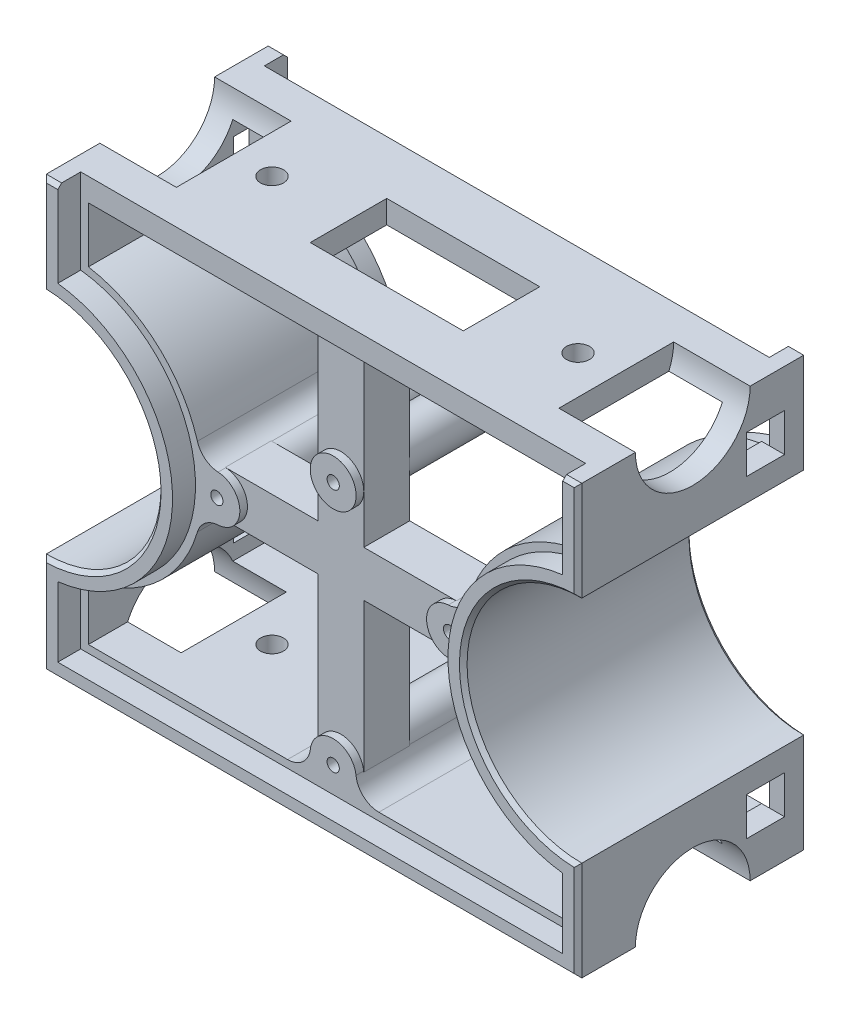
SolidWorks part; units mm, degrees
ref_plane "Front Plane" through (0, 0, 0) normal (0, 0, 1) x (1, 0, 0)
ref_plane "Top Plane" through (0, 0, 0) normal (0, 1, 0) x (1, 0, 0)
ref_plane "Right Plane" through (0, 0, 0) normal (1, 0, 0) x (0, 0, -1)
sketch "Sketch1" plane through (0, 0, 0) normal (0, 1, 0) x (1, 0, 0)
  line L1 (-35, -15) -> (35, -15)
  line L2 (-35, -15) -> (-35, 15)
  line L3 (-35, 15) -> (35, 15)
  line L4 (35, -15) -> (35, 15)
  line L5 (-35, -15) -> (35, 15) construction
  line L6 (-35, 15) -> (35, -15) construction
  point P0 (0, 0)
  dimension "D1" = 30
  dimension "D2" = 70
extrude "Boss-Extrude1" add sketch "Sketch1" along normal blind 56
sketch "Sketch2" plane through (0, 0, -15) normal (0, 0, -1) x (-1, 0, 0)
  line L0 (35, 56) -> (35, 0) construction
  line L1 (32, 53) -> (-32, 53)
  line L2 (32, 53) -> (32, 45.7482)
  line L3 (32, 3) -> (-32, 3)
  line L4 (-32, 53) -> (-32, 45.7482)
  line L5 (32, 53) -> (-32, 3) construction
  line L6 (32, 3) -> (-32, 53) construction
  line L7 (-35, 56) -> (-35, 0) construction
  line L8 (-35, 0) -> (35, 0) construction
  line L9 (-35, 56) -> (35, 56) construction
  line L10 (-32, 10.2518) -> (-32, 3)
  line L11 (32, 10.2518) -> (32, 3)
  line L12 (-33, 54) -> (-33, 44.8819)
  line L13 (33, 54) -> (33, 44.8819)
  line L14 (33, 2) -> (-33, 2)
  line L15 (-33, 11.1181) -> (-33, 2)
  line L16 (33, 11.1181) -> (33, 2)
  line L17 (33, 54) -> (-33, 54)
  arc A0 (-32, 10.2518) -> (-32, 45.7482) centre (-35, 28) ccw
  arc A1 (32, 45.7482) -> (32, 10.2518) centre (35, 28) ccw
  arc A2 (-33, 11.1181) -> (-33, 44.8819) centre (-35, 28) ccw
  arc A3 (33, 44.8819) -> (33, 11.1181) centre (35, 28) ccw
  point P0 (0, 28)
  dimension "D5" = 36
  dimension "D6" = 36
  dimension "D9" = 0
  dimension "D10" = 17
  dimension "D13" = 0
  dimension "D14" = 17
  dimension "D1" = 3
  dimension "D2" = 3
  dimension "D3" = 3
  dimension "D4" = 3
  dimension "D7" = 1
  dimension "D8" = 1
  dimension "D11" = 1
  dimension "D12" = 1
extrude "Cut-Extrude1" cut sketch "Sketch2" against normal through all contours A1 L11 L3 L10 A0 L4 L1 L2
sketch "Sketch3" plane through (0, 0, 0) normal (0, -1, 0) x (1, 0, 0)
  circle A0 centre (20, 0) radius 1.5
  circle A1 centre (-20, 0) radius 1.5
  dimension "D1" = 3
  dimension "D2" = 3
  dimension "D3" = 20
  dimension "D4" = 20
extrude "Cut-Extrude2" cut sketch "Sketch3" against normal blind 5 and the other way through all
sketch "Sketch4" plane through (35, 0, 0) normal (1, 0, 0) x (0, 0, -1)
  line L0 (-15, 56) -> (15, 56) construction
  line L1 (-15, 0) -> (15, 0) construction
  circle A0 centre (0, 56) radius 7.5
  circle A1 centre (0, 0) radius 7.5
  dimension "D1" = 15
  dimension "D2" = 15
extrude "Cut-Extrude5" cut sketch "Sketch4" against normal blind 10
sketch "Sketch6" plane through (0, 0, 15) normal (0, 0, 1) x (1, 0, 0)
  line L0 (-35, 56) -> (-35, 0) construction
  line L1 (35, 56) -> (35, 0) construction
  circle A0 centre (-35, 28) radius 15
  circle A1 centre (35, 28) radius 15
  dimension "D1" = 30
extrude "Cut-Extrude7" cut sketch "Sketch6" against normal through all
sketch "Sketch7" plane through (0, 56, 0) normal (0, 1, 0) x (1, 0, 0)
  line L1 (-10, 5) -> (10, 5)
  line L2 (-10, 5) -> (-10, -5)
  line L3 (-10, -5) -> (10, -5)
  line L4 (10, 5) -> (10, -5)
  line L5 (-10, 5) -> (10, -5) construction
  line L6 (-10, -5) -> (10, 5) construction
  point P0 (0, 0)
  dimension "D1" = 20
  dimension "D2" = 10
extrude "Cut-Extrude8" cut sketch "Sketch7" against normal blind 10
sketch "Sketch8" plane through (0, 56, 0) normal (0, 1, 0) x (1, 0, 0)
  circle A0 centre (20, 0) radius 1.5
  circle A1 centre (-20, 0) radius 1.5
  dimension "D1" = 3
  dimension "D2" = 3
  dimension "D3" = 40
  dimension "D4" = 20
extrude "Cut-Extrude10" cut sketch "Sketch8" against normal blind 10
extrude "Cut-Extrude11" cut sketch "Sketch2<3>" against normal blind 3
sketch "Sketch2<3>" plane through (0, 0, -15) normal (0, 0, -1) x (-1, 0, 0) same geometry as "Sketch2"
sketch "Sketch11" plane through (0, 0, 15) normal (0, 0, 1) x (1, 0, 0)
  line L0 (17, 28) -> (-17, 28) construction
  line L1 (0, 53) -> (0, 3) construction
  line L2 (-32, 3) -> (32, 3) construction
  line L3 (-3, 3) -> (3, 3)
  line L4 (3, 3) -> (3, 25)
  line L5 (3, 25) -> (17.2518, 25)
  line L6 (-3, 3) -> (-3, 25)
  line L7 (-3, 25) -> (-17.2518, 25)
  line L8 (-3, 31) -> (-17.2518, 31)
  line L9 (-3, 53) -> (-3, 31)
  line L10 (-3, 53) -> (3, 53)
  line L11 (3, 53) -> (3, 31)
  line L12 (3, 31) -> (17.2518, 31)
  arc A0 (32, 45.7482) -> (32, 10.2518) centre (35, 28) ccw construction
  arc A2 (17.2518, 31) -> (17.2518, 25) centre (35, 28) ccw
  arc A3 (-17.2518, 31) -> (-17.2518, 25) centre (-35, 28) cw
  point P13 (0, 28)
  dimension "D1" = 3
  dimension "D2" = 3
extrude "Boss-Extrude2" add sketch "Sketch11" against normal blind 6 from offset 4 offset against normal yes
chamfer "Chamfer1" distance 0.5 angle 45 16 edges at (0, 56, 15) (35, 49.5, 15) (20, 28, 15) (35, 6.5, 15) (0, 0, 15) (-35, 6.5, 15) (-20, 28, 15) (-35, 49.5, 15) (-17, 28, 15) (-32, 6.6259, 15) (0, 3, 15) (32, 6.6259, 15) (17, 28, 15) (32, 49.3741, 15) (0, 53, 15) (-32, 49.3741, 15)
chamfer "Chamfer2" distance 0.5 angle 45 8 edges at (-35, 6.5, -15) (-20, 28, -15) (-35, 49.5, -15) (0, 56, -15) (35, 49.5, -15) (20, 28, -15) (0, 0, -15) (35, 6.5, -15)
sketch "Sketch10" plane through (0, 0, -15) normal (0, 0, -1) x (-1, 0, 0)
  line L0 (-35, 56) -> (35, 56) construction
  line L1 (33, 54) -> (-33, 54)
  line L2 (33, 54) -> (33, 56)
  line L3 (33, 56) -> (-33, 56)
  line L4 (-33, 54) -> (-33, 56)
  line L5 (-33, 54) -> (-33, 44.8819) construction
extrude "Cut-Extrude13" cut sketch "Sketch10" against normal blind 3
mirror "Mirror2" about plane through (0, 0, 0) normal (0, 0, 1) of "Cut-Extrude13", "Cut-Extrude11"
sketch "Sketch12" plane through (35, 0, 0) normal (1, 0, 0) x (0, 0, -1)
  line L0 (15, 12.5081) -> (15, 0.5) construction
  line L1 (7, 10) -> (12, 10)
  line L2 (7, 10) -> (7, 5)
  line L3 (7, 5) -> (12, 5)
  line L4 (12, 10) -> (12, 5)
  line L5 (7.5, 0) -> (14.5, 0) construction
  line L6 (-15, 28) -> (15, 28) construction
  line L7 (-15, 43.4919) -> (-15, 12.5081) construction
  line L8 (15, 12.5081) -> (15, 43.4919) construction
  line L9 (12, 46) -> (12, 51)
  line L10 (7, 51) -> (12, 51)
  line L11 (7, 46) -> (7, 51)
  line L12 (7, 46) -> (12, 46)
  dimension "D1" = 5
  dimension "D2" = 3
  dimension "D3" = 5
  dimension "D4" = 5
extrude "Cut-Extrude14" cut sketch "Sketch12" against normal up to surface (3 mm away) up to face at (32, 6.1673, 0)
mirror "Mirror3" about plane through (0, 0, 0) normal (1, 0, 0) of "Cut-Extrude14"
mirror "Mirror4" about plane through (0, 0, 0) normal (1, 0, 0) of "Cut-Extrude5"
sketch "Sketch13" plane through (0, 0, -12) normal (0, 0, -1) x (-1, 0, 0)
  line L0 (-17, 28) -> (17, 28) construction
  line L1 (0, 53) -> (0, 3) construction
  line L2 (32, 53) -> (-32, 53) construction
  line L3 (-32, 3) -> (32, 3) construction
  line L4 (3, 3) -> (-3, 3) construction
  line L5 (-1.8648, 3) -> (1.8648, 3)
  line L6 (-33, 2) -> (33, 2) construction
  arc A0 (-17.2518, 25) -> (-17.2518, 31) centre (-35, 28) ccw construction
  arc A1 (32, 45.7482) -> (32, 10.2518) centre (35, 28) ccw construction
  arc A2 (-17.1459, 30.2873) -> (-17.1459, 25.7127) centre (-15.2047, 28) cw
  arc A3 (-32, 10.2518) -> (-32, 45.7482) centre (-35, 28) ccw construction
  arc A4 (-17.1459, 30.2873) -> (-17.1459, 25.7127) centre (-35.2047, 28) cw
  arc A5 (17.1459, 30.2873) -> (17.1459, 25.7127) centre (35.2047, 28) ccw
  arc A6 (17.1459, 30.2873) -> (17.1459, 25.7127) centre (15.2047, 28) ccw
  arc A7 (-1.8648, 3) -> (1.8648, 3) centre (0, 5.35) cw
  circle A8 centre (0, 37.35) radius 3
  dimension "D1" = 3
  dimension "D3" = 3
  dimension "D2" = 20
  dimension "D4" = 3.35
  dimension "D5" = 35.35
extrude "Boss-Extrude3" add sketch "Sketch13" against normal up to surface (24 mm away) up to face at (0, 28.5, 12)
hole_wizard "Tap Drill for M2x0.4 Tap1" positions "Sketch14" profile "Sketch15" hole size "M2x0.4" standard "ANSI Metric" end condition through all
sketch "Sketch14" plane through (0, 0, -12) normal (0, 0, -1) x (-1, 0, 0)
  point P0 (-15.2047, 28)
  point P3 (15.2047, 28)
  point P7 (0, 5.35)
  point P10 (0, 37.35)
sketch "Sketch15" plane through (15.2047, 28, -12) normal (1, 0, 0) x (0, 1, 0)
  line L0 (0, 0) -> (0, 27)
  line L1 (0, 27) -> (0.8, 27)
  line L2 (0.8, 27) -> (0.8, 0)
  line L5 (0.8, 0) -> (0, 0)
  line L11 (0, -6.35) -> (0, 107.95) construction
  dimension "Thru Hole Dia." = 1.6
  dimension "Thru Hole Depth" = 27
fillet "Fillet1" radius 3 6 edges at (-1.8648, 3, -3.5) (1.8648, 3, -3.5)
